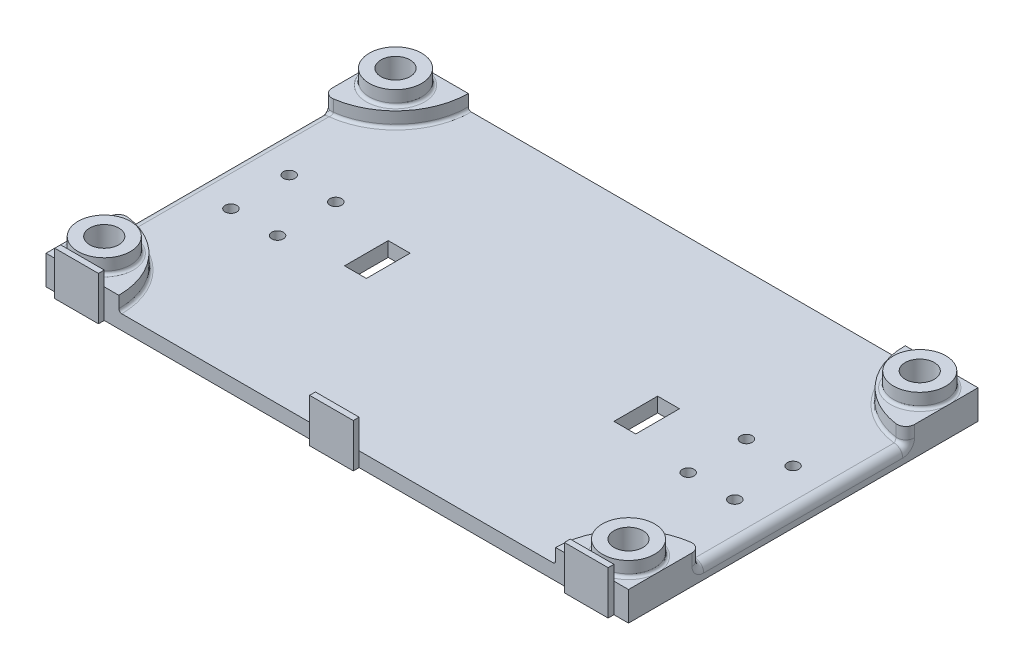
SolidWorks part; units mm, degrees
ref_plane "Front Plane" through (0, 0, 0) normal (0, 0, 1) x (1, 0, 0)
ref_plane "Top Plane" through (0, 0, 0) normal (0, 1, 0) x (1, 0, 0)
ref_plane "Right Plane" through (0, 0, 0) normal (1, 0, 0) x (0, 0, -1)
sketch "Sketch1" plane through (0, 0, 0) normal (0, 1, 0) x (1, 0, 0)
  line L1 (100, -60) -> (-100, -60)
  line L2 (100, -60) -> (100, 60)
  line L3 (100, 60) -> (-100, 60)
  line L4 (-100, -60) -> (-100, 60)
  line L5 (100, -60) -> (-100, 60) construction
  line L6 (100, 60) -> (-100, -60) construction
  point P0 (0, 0)
  dimension "D1" = 200
  dimension "D2" = 120
extrude "Boss-Extrude3" add sketch "Sketch1" along normal blind 5
sketch "Sketch3" plane through (0, 5, 0) normal (0, 1, 0) x (1, 0, 0)
  line L0 (-100, 60) -> (-80, 40) construction
  line L5 (100, 60) -> (-100, 60) construction
  line L6 (-100, 60) -> (-100, -60) construction
  line L7 (80, 40) -> (100, 60) construction
  line L8 (-80, -40) -> (-100, -60) construction
  line L9 (-100, 35) -> (-100, 60)
  line L10 (-100, 60) -> (-75, 60)
  line L11 (0, -2.75) -> (0, 2.75) construction
  line L12 (80, -40) -> (100, -60) construction
  line L13 (100, 35) -> (100, 60)
  line L14 (100, 60) -> (75, 60)
  line L15 (-2.75, 0) -> (2.75, 0) construction
  line L16 (100, -60) -> (75, -60)
  line L17 (100, -35) -> (100, -60)
  line L18 (-100, -35) -> (-100, -60)
  line L19 (-100, -60) -> (-75, -60)
  circle A0 centre (-90, 50) radius 5
  circle A2 centre (90, -50) radius 5
  circle A4 centre (90, 50) radius 5
  circle A5 centre (-90, -50) radius 5
  arc A6 (-75, 60) -> (-100, 35) centre (-100, 60) cw
  circle A7 centre (90, 50) radius 5
  arc A8 (75, 60) -> (100, 35) centre (100, 60) ccw
  circle A9 centre (90, -50) radius 5
  arc A10 (75, -60) -> (100, -35) centre (100, -60) cw
  circle A11 centre (-90, -50) radius 5
  arc A12 (-75, -60) -> (-100, -35) centre (-100, -60) ccw
  point P0 (0, 0)
  line M5 (-100, 60) -> (-100, -60)
  line M6 (-100, -60) -> (100, -60)
  line M7 (100, -60) -> (100, 60)
  line M8 (100, 60) -> (-100, 60)
  dimension "D3" = 10
  dimension "D4" = 10
  dimension "D5" = 10
  dimension "D6" = 10
  dimension "D7" = 25
  dimension "D1" = 160
  dimension "D2" = 80
extrude "Boss-Extrude4" add sketch "Sketch3" along normal blind 5 contours A6 A0 M8 M5 | A12 A5 M6 M5 | A8 A4 M8 M7 | A10 A2 M6 M7 region at (-99.6464, 5, -47.5) region at (-82.5723, 5, 42.5723) region at (87.5, 5, -59.6464) region at (82.5723, 5, 42.5723)
sketch "Sketch8" plane through (0, 10, 0) normal (0, 1, 0) x (1, 0, 0)
  line L0 (0, -2.75) -> (0, 2.75) construction
  line L1 (-2.75, 0) -> (2.75, 0) construction
  circle A0 centre (-90, 50) radius 9
  circle A1 centre (-90, 50) radius 5
  circle A2 centre (90, 50) radius 9
  circle A3 centre (90, 50) radius 5
  circle A4 centre (90, -50) radius 9
  circle A5 centre (90, -50) radius 5
  circle A6 centre (-90, -50) radius 5
  circle A7 centre (-90, -50) radius 9
  dimension "D1" = 18
extrude "Boss-Extrude5" add sketch "Sketch8" along normal blind 5
fillet "Fillet1" radius 1 8 edges at (82.3223, 5, -42.3223) (-82.3223, 5, -42.3223) (82.3223, 5, 42.3223) (-82.3223, 5, 42.3223) (-90, 10, 41) (90, 10, -59) (-90, 10, -41) (90, 10, 59)
sketch "Sketch10" plane through (0, 0, 60) normal (0, 0, 1) x (1, 0, 0)
  line L0 (-100, 0) -> (100, 0) construction
  line L5 (-95, 0) -> (-80, 0)
  line L6 (-95, 0) -> (-95, 15)
  line L7 (-95, 15) -> (-80, 15)
  line L8 (-80, 0) -> (-80, 15)
  line L9 (-100, 10) -> (-100, 0) construction
  line L10 (0, -2.75) -> (0, 2.75) construction
  line L11 (95, 0) -> (80, 0)
  line L12 (95, 0) -> (95, 15)
  line L13 (95, 15) -> (80, 15)
  line L14 (80, 0) -> (80, 15)
  line L16 (-7.5, 0) -> (7.5, 0)
  line L17 (-7.5, 0) -> (-7.5, 15)
  line L18 (-7.5, 15) -> (7.5, 15)
  line L19 (7.5, 0) -> (7.5, 15)
  point P18 (0, 0)
  point P19 (0, 0)
  point P21 (0, 0)
  point P22 (-15.244, -1.9886)
  point P23 (0, 0)
  dimension "D1" = 15
  dimension "D2" = 15
  dimension "D3" = 5
  dimension "D4" = 15
  dimension "D5" = 15
extrude "Boss-Extrude6" add sketch "Sketch10" along normal blind 2
fillet "Fillet2" radius 3 5 edges at (-100, 8, -35) (-100, 5.2929, -34.7071) (-100, 8, 35) (-100, 5.2929, 34.7071) (-100, 5, 0)
fillet "Fillet3" radius 3 5 edges at (100, 8, 35) (100, 5.2929, 34.7071) (100, 8, -35) (100, 5.2929, -34.7071) (100, 5, 0)
sketch "Sketch12" plane through (0, 0, 0) normal (0, -1, 0) x (1, 0, 0)
  line L0 (-100, -60) -> (-100, 60) construction
  line L1 (2.75, 0) -> (-2.75, 0) construction
  line L2 (0, -2.75) -> (0, 2.75) construction
  line L3 (50, -7.5) -> (42.5, -7.5)
  line L8 (-50, 7.5) -> (-42.5, 7.5)
  line L9 (-50, 7.5) -> (-50, -7.5)
  line L10 (-50, -7.5) -> (-42.5, -7.5)
  line L11 (-42.5, 7.5) -> (-42.5, -7.5)
  line L12 (42.5, 7.5) -> (42.5, -7.5)
  line L13 (50, 7.5) -> (42.5, 7.5)
  line L14 (50, 7.5) -> (50, -7.5)
  circle A0 centre (-86.5, 10) radius 2
  circle A1 centre (-70.5, 10) radius 2
  circle A2 centre (-70.5, -10) radius 2
  circle A3 centre (-86.5, -10) radius 2
  circle A4 centre (86.5, -10) radius 2
  circle A5 centre (70.5, -10) radius 2
  circle A6 centre (70.5, 10) radius 2
  circle A7 centre (86.5, 10) radius 2
  point P6 (-100, 0)
  point P28 (-50, 0)
  dimension "D1" = 13.5
  dimension "D3" = 16
  dimension "D2" = 10
  dimension "D4" = 15
  dimension "D5" = 7.5
  dimension "D6" = 50
extrude "Cut-Extrude1" cut sketch "Sketch12" against normal through all
